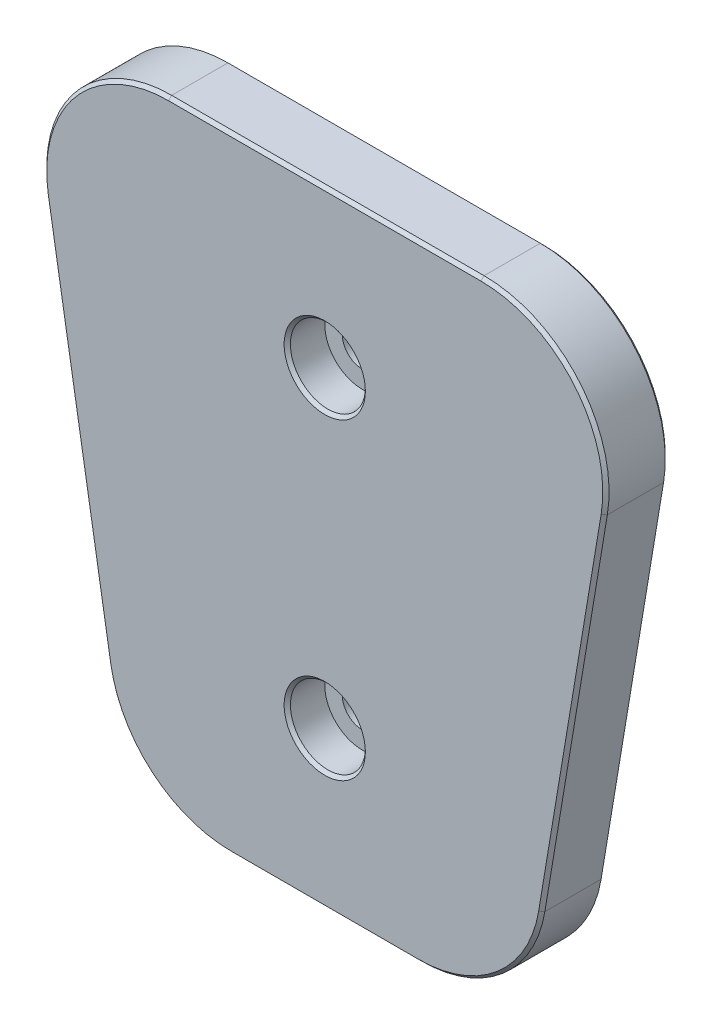
SolidWorks part; units mm, degrees
ref_plane "Front Plane" through (0, 0, 0) normal (0, 0, 1) x (1, 0, 0)
ref_plane "Top Plane" through (0, 0, 0) normal (0, 1, 0) x (1, 0, 0)
ref_plane "Right Plane" through (0, 0, 0) normal (1, 0, 0) x (0, 0, -1)
sketch "Sketch3" plane through (0, 0, 0) normal (0, 0, 1) x (1, 0, 0)
  line L0 (-6.3553, -23.288) -> (3.6447, -83.288)
  line L1 (13.3726, 0) -> (63.3726, 0)
  line L5 (23.3726, -100) -> (53.3726, -100)
  line L6 (73.1005, -83.288) -> (83.1005, -23.288)
  line L7 (38.3726, 0) -> (38.3726, -173.3588) construction
  arc A0 (63.3726, 0) -> (83.1005, -23.288) centre (63.3726, -20) cw
  arc A1 (13.3726, 0) -> (-6.3553, -23.288) centre (13.3726, -20) ccw
  arc A2 (53.3726, -100) -> (73.1005, -83.288) centre (53.3726, -80) ccw
  arc A3 (3.6447, -83.288) -> (23.3726, -100) centre (23.3726, -80) ccw
  point P7 (120, 0)
  point P10 (0, 0)
  point P13 (38.3726, -100)
  dimension "D3" = 20
  dimension "D5" = 20
  dimension "D6" = 30
  dimension "D1" = 50
  dimension "D2" = 100
  dimension "D4" = 0
extrude "Boss-Extrude1" add sketch "Sketch3" along normal blind 10 contours A3 L5 A2 L6 A0 L1 A1 L0
sketch "Sketch4" plane through (0, 0, 10) normal (0, 0, 1) x (1, 0, 0)
  line L0 (38.3726, 0) -> (38.3726, -50) construction
  line L1 (13.3726, 0) -> (63.3726, 0) construction
  line L2 (23.3726, -100) -> (53.3726, -100) construction
  line L3 (38.3726, 0) -> (38.3726, -50) construction
  line L4 (38.3726, -50) -> (38.3726, -100) construction
  line L5 (38.3726, -50) -> (38.3726, -100) construction
  circle A1 centre (38.3726, -25) radius 6
  circle A2 centre (38.3726, -75) radius 6
  dimension "D1" = 12
  dimension "D3" = 12
  dimension "D2" = 25
  dimension "D4" = 25
extrude "Cut-Extrude1" cut sketch "Sketch4" against normal blind 6
sketch "Sketch5" plane through (0, 0, 4) normal (0, 0, 1) x (1, 0, 0)
  circle A0 centre (38.3726, -25) radius 3.2
  circle A2 centre (38.3726, -75) radius 3.2
  dimension "D1" = 6.4
  dimension "D3" = 6.4
extrude "Cut-Extrude2" cut sketch "Sketch5" against normal through all
chamfer "Chamfer1" distance 0.5 angle 45 20 edges at (10.4451, -95.2604, 0) (38.3726, -100, 0) (66.3001, -95.2604, 0) (78.1005, -53.288, 0) (78.633, -7.0725, 0) (38.3726, 0, 0) (-1.8878, -7.0725, 0) (-1.3553, -53.288, 0) (41.5726, -75, 0) (41.5726, -25, 0) (-1.8878, -7.0725, 10) (38.3726, 0, 10) (78.633, -7.0725, 10) (78.1005, -53.288, 10) (66.3001, -95.2604, 10) (38.3726, -100, 10) (10.4451, -95.2604, 10) (-1.3553, -53.288, 10) (44.3726, -25, 10) (44.3726, -75, 10)
equation "\"D3@Sketch4\"= \"D1@Sketch4\""
equation "\"D3@Sketch5\"=\"D1@Sketch5\""
